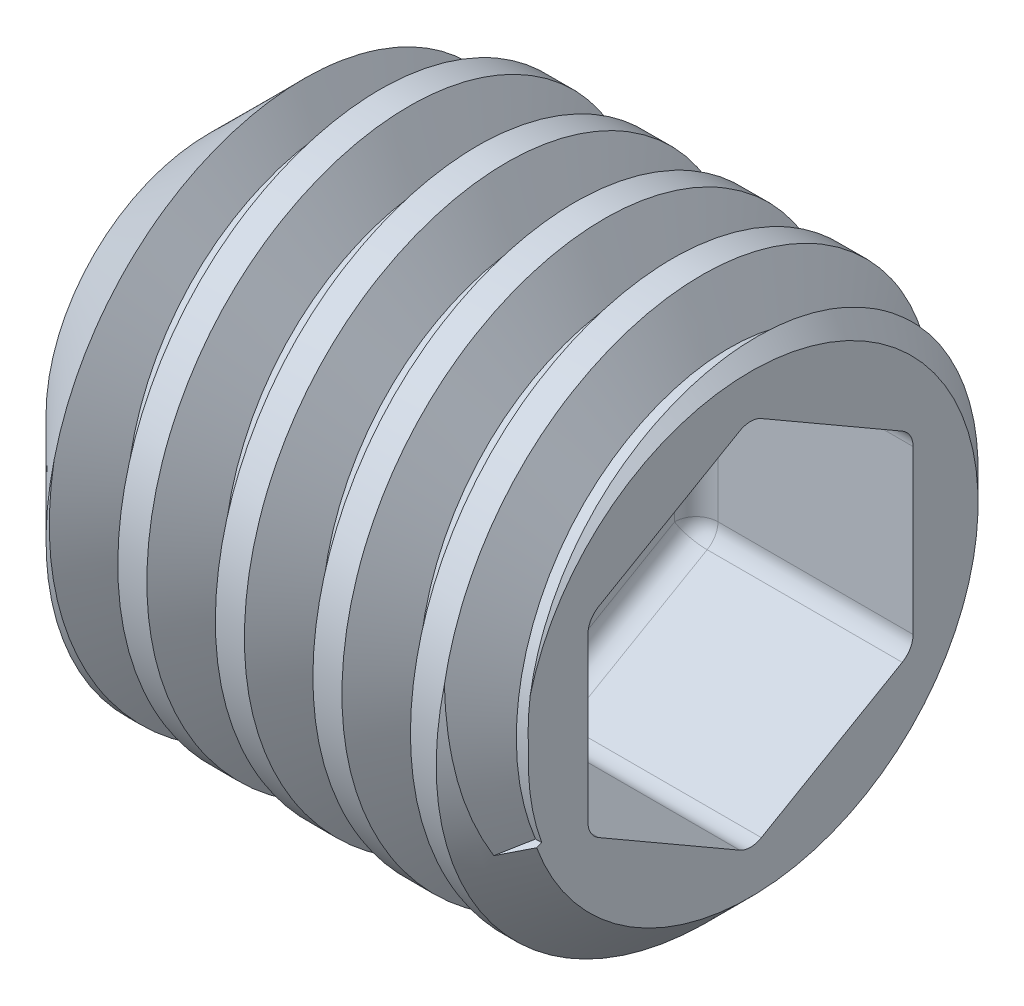
SolidWorks part; units mm, degrees
material "Простая углеродистая сталь"
ref_plane "Спереди" through (0, 0, 0) normal (0, 0, 1) x (1, 0, 0)
ref_plane "Сверху" through (0, 0, 0) normal (0, 1, 0) x (1, 0, 0)
ref_plane "Справа" through (0, 0, 0) normal (1, 0, 0) x (0, 0, -1)
sketch "Эскиз1" plane through (0, 0, 0) normal (0, 0, 1) x (1, 0, 0)
  line L0 (0, 0) -> (4.1891, 0) construction
  line L1 (0, 0) -> (0, 0.75)
  line L2 (0, 0.75) -> (0.5, 1.25)
  line L3 (0.5, 1.25) -> (2.3, 1.25)
  line L4 (2.5, 1.05) -> (2.5, 0)
  line L5 (0, 0) -> (2.5, 0)
  line L6 (2.3, 1.25) -> (2.5, 1.05)
  point P6 (2.5, 1.25)
  dimension "D1" = 2.5
  dimension "D2" = 45
  dimension "D3" = 0.5
  dimension "D4" = 2.5
  dimension "D5" = 0.2
  dimension "D6" = 45
revolve "Повернуть1" add sketch "Эскиз1" angle 360 about L0
sketch "Эскиз2" plane through (2.5, 0, 0) normal (1, 0, 0) x (0, 0, -1)
  line L1 (0.75, 0.433) -> (0, 0.866)
  line L2 (0, 0.866) -> (-0.75, 0.433)
  line L3 (-0.75, 0.433) -> (-0.75, -0.433)
  line L4 (-0.75, -0.433) -> (0, -0.866)
  line L5 (0, -0.866) -> (0.75, -0.433)
  line L6 (0.75, -0.433) -> (0.75, 0.433)
  circle A0 centre (0, 0) radius 0.75 construction
  dimension "D1" = 1.5
extrude "Вырез-Вытянуть1" cut sketch "Эскиз2" against normal blind 1
fillet "Скругление1" radius 0.1 12 edges at (1.5, -0.6495, -0.375) (1.5, -0.6495, 0.375) (1.5, 0, 0.75) (1.5, 0.6495, 0.375) (1.5, 0.6495, -0.375) (1.5, 0, -0.75) (2, 0.433, -0.75) (2, -0.433, -0.75) (2, -0.866, 0) (2, -0.433, 0.75) (2, 0.433, 0.75) (2, 0.866, 0)
sketch "Эскиз3" plane through (0, 0, 0) normal (0, 1, 0) x (1, 0, 0)
  line L0 (0, 0) -> (2.9254, 0) construction
  line L1 (-0.0281, 1.025) -> (0.0281, 1.025)
  line L2 (0.0281, 1.025) -> (0.158, 1.25)
  line L3 (0.158, 1.25) -> (0.2143, 1.25)
  line L4 (0.2143, 1.25) -> (0.2143, 1.3582)
  line L5 (0.2143, 1.3582) -> (-0.2143, 1.3582)
  line L6 (-0.2143, 1.3582) -> (-0.2143, 1.25)
  line L7 (-0.2143, 1.25) -> (-0.158, 1.25)
  line L8 (-0.158, 1.25) -> (-0.0281, 1.025)
  line L9 (0, 1.025) -> (0, 2.06) construction
  line L10 (2.3, 1.25) -> (0.5, 1.25) construction
  line L11 (0, 0.75) -> (0, -0.75) construction
  dimension "D1" = 2.05
  dimension "D2" = 0.0563
  dimension "D3" = 0.0563
  dimension "D4" = 60
sketch "Эскиз4" plane through (0, 0, 0) normal (-1, 0, 0) x (0, 0, 1)
  circle A0 centre (0, 0) radius 1.025
curve "Спираль1" pitch 0.45 height 2.5 turns 5.5556
sweep "Вырез-По траектории1" cut profiles "Эскиз3" path "Спираль1"
